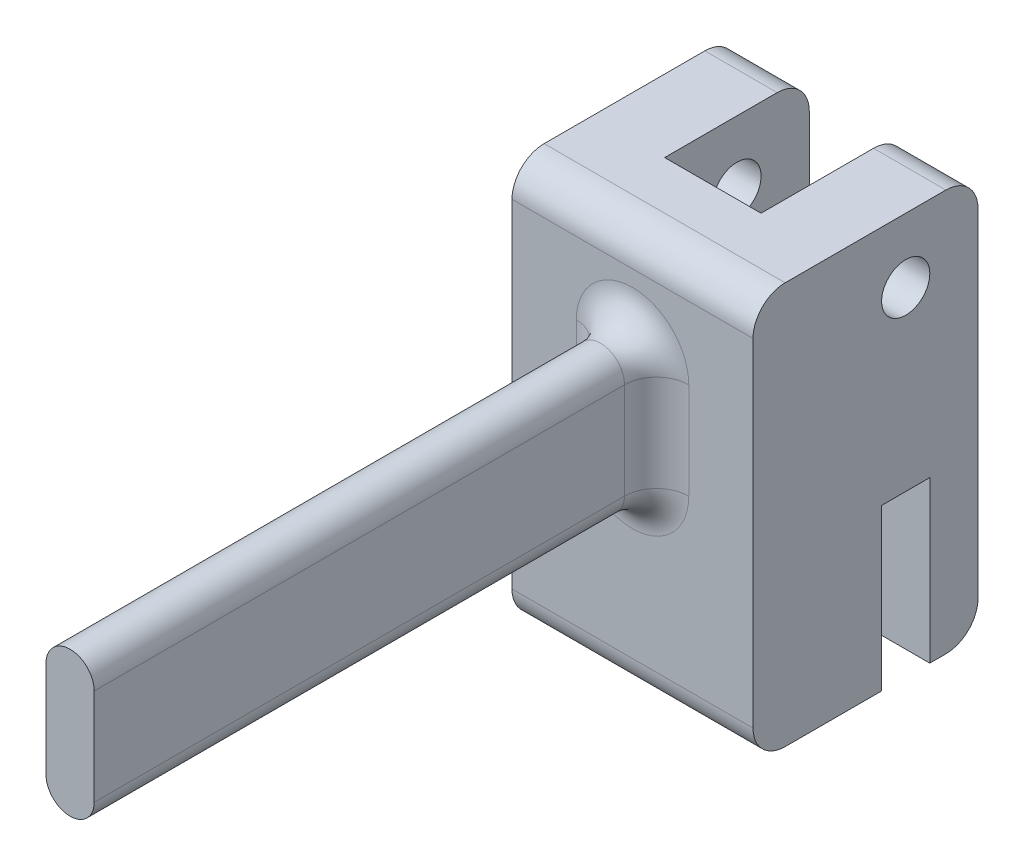
SolidWorks part; units mm, degrees
ref_plane "Alzado" through (0, 0, 0) normal (0, 0, 1) x (1, 0, 0)
ref_plane "Planta" through (0, 0, 0) normal (0, 1, 0) x (1, 0, 0)
ref_plane "Vista lateral" through (0, 0, 0) normal (1, 0, 0) x (0, 0, -1)
sketch "Croquis2" plane through (0, 0, 0) normal (0, 0, 1) x (1, 0, 0)
  line L1 (-7.5, 7.5) -> (7.5, 7.5)
  line L2 (-7.5, 7.5) -> (-7.5, -7.5)
  line L3 (-7.5, -7.5) -> (7.5, -7.5)
  line L4 (7.5, 7.5) -> (7.5, -7.5)
  point P4 (0, -7.5)
  point P6 (7.5, 0)
  dimension "D1" = 15
  dimension "D2" = 15
extrude "Saliente-Extruir1" add sketch "Croquis2" along normal mid plane 9
sketch "Croquis3" plane through (0, 0, 0) normal (0, 0, 1) x (1, 0, 0)
  line L0 (-7.5, 7.5) -> (-7.5, -7.5) construction
  line L1 (-7.5, 2.5) -> (7.5, 2.5)
  line L2 (-7.5, 2.5) -> (-7.5, -7.5)
  line L3 (-7.5, -7.5) -> (7.5, -7.5)
  line L4 (7.5, 2.5) -> (7.5, -7.5)
  line L5 (7.5, 7.5) -> (-7.5, 7.5) construction
  dimension "D1" = 5
extrude "Cortar-Extruir1" cut sketch "Croquis3" against normal mid plane 3
sketch "Croquis4" plane through (0, 0, 0) normal (0, 0, 1) x (1, 0, 0)
  line L0 (7.5, 7.5) -> (-7.5, 7.5) construction
  line L1 (-1.5, 0) -> (-1.5, -7.5)
  line L2 (-7.5, -7.5) -> (7.5, -7.5) construction
  line L3 (1.5, 0) -> (1.5, -7.5)
  line L4 (-1.5, -7.5) -> (1.5, -7.5)
  arc A0 (1.5, 0) -> (-1.5, 0) centre (0, 0) ccw
  dimension "D2" = 3
  dimension "D1" = 7.5
extrude "Cortar-Extruir2" cut sketch "Croquis4" against normal through all
sketch "Croquis10" plane through (0, 7.5, 0) normal (0, 1, 0) x (1, 0, 0)
  line L0 (-3, 4.5) -> (-3, -4.5)
  line L1 (3, 4.5) -> (3, -4.5)
  line L2 (0, 4.5) -> (0, -4.5) construction
  line L3 (-3, 4.5) -> (-7.5, 4.5)
  line L4 (7.5, 4.5) -> (-7.5, 4.5)
  line L5 (-7.5, 4.5) -> (-7.5, -4.5)
  line L6 (-7.5, -4.5) -> (7.5, -4.5)
  line L7 (7.5, -4.5) -> (7.5, 4.5)
  line L8 (7.5, 4.5) -> (3, 4.5)
  line L9 (-7.5, 4.5) -> (-7.5, -4.5)
  line L10 (-7.5, -4.5) -> (-3, -4.5)
  line L11 (7.5, -4.5) -> (7.5, 4.5)
  line L12 (3, -4.5) -> (7.5, -4.5)
  line L13 (7.5, 4.5) -> (-7.5, 4.5) construction
  point P11 (0, 0)
  dimension "D2" = 6
  dimension "D1" = 0
extrude "Saliente-Extruir4" add sketch "Croquis10" along normal blind 10
sketch "Croquis7" plane through (0, 0, 0) normal (1, 0, 0) x (0, 0, -1)
  line L1 (-4.5, 17.5) -> (4.5, 17.5) construction
  circle A0 centre (0, 13.5) radius 1.5
  dimension "D1" = 3
  dimension "D2" = 4
extrude "Cortar-Extruir3" cut sketch "Croquis7" against normal through all both and the other way through all
sketch "Croquis12" plane through (0, 0, 4.5) normal (0, 0, 1) x (1, 0, 0)
  line L0 (7.5, -7.5) -> (7.5, 17.5) construction
  line L1 (-7.5, 17.5) -> (7.5, 17.5)
  line L2 (-7.5, 17.5) -> (-7.5, -7.5)
  line L3 (-7.5, -7.5) -> (7.5, -7.5)
  line L4 (7.5, 17.5) -> (7.5, -7.5)
  line L5 (-7.5, -7.5) -> (7.5, -7.5) construction
extrude "Saliente-Extruir5" add sketch "Croquis12" along normal blind 5
fillet "Redondeo2" radius 2 6 edges at (5.25, 17.5, -4.5) (-5.25, 17.5, -4.5) (0, 17.5, 9.5) (-4.5, -7.5, -4.5) (4.5, -7.5, -4.5) (0, -7.5, 9.5)
sketch "Croquis11" plane through (0, 0, 9.5) normal (0, 0, 1) x (1, 0, 0)
  line L0 (0, 11) -> (0, 5) construction
  line L1 (1.5, 11) -> (1.5, 5)
  line L2 (-1.5, 11) -> (-1.5, 5)
  arc A1 (1.5, 11) -> (-1.5, 11) centre (0, 11) ccw
  arc A2 (-1.5, 5) -> (1.5, 5) centre (0, 5) ccw
  point P5 (0, 8)
  dimension "D1" = 8
  dimension "D3" = 1.5
  dimension "D2" = 6
extrude "Saliente-Extruir6" add sketch "Croquis11" along normal blind 35
fillet "Redondeo4" radius 2 4 edges at (0, 12.5, 9.5) (1.5, 8, 9.5) (0, 3.5, 9.5) (-1.5, 8, 9.5)
